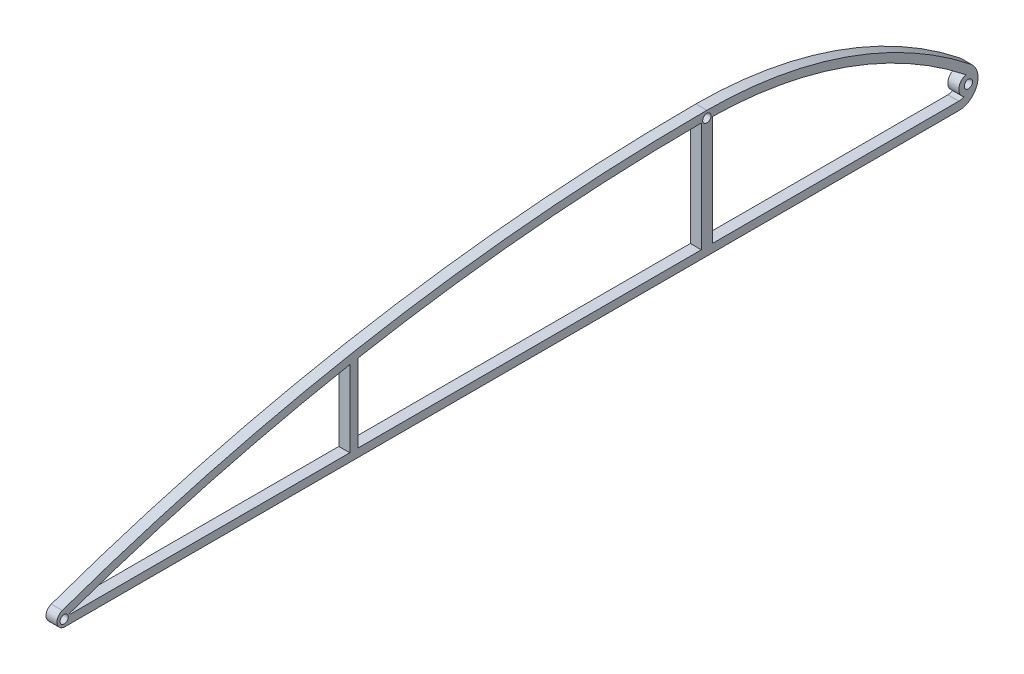
SolidWorks part; units mm, degrees
other "Marquage1"
sketch "Esquisse8" plane through (8, 0, -172.8424) normal (1, 0, 0) x (0, 0, -1)
other "Marquage2"
sketch "Esquisse10" plane through (-6, 20, -172.8424) normal (-0.8365, 0.2588, -0.483) x (-0.5, 0, 0.866)
other "Marquage3"
sketch "Esquisse11" plane through (0, 0, 0) normal (-0.0501, -0.1345, 0.9896) x (0.9942, 0.0873, 0.0622)
ref_plane "Plan de face" through (0, 0, 0) normal (0, 0, 1) x (1, 0, 0)
ref_plane "Plan de dessus" through (0, 0, 0) normal (0, 1, 0) x (1, 0, 0)
ref_plane "Plan de droite" through (0, 0, 0) normal (1, 0, 0) x (0, 0, -1)
sketch "Esquisse2" plane through (0, 0, 0) normal (1, 0, 0) x (0, 0, -1)
  line L0 (0, 0) -> (170.8732, 0)
  arc A1 (173.0499, 6.2408) -> (125, 23) centre (125, -54.2609) ccw
  arc A3 (170.8732, 0) -> (173.0499, 6.2408) centre (170.8732, 3.5) ccw
  arc A4 (125, 23) -> (0, 0) centre (125, -328.1739) ccw
  point P10 (180, 0)
  dimension "D1" = 180
  dimension "D2" = 3.5
  dimension "D3" = 23
  dimension "D4" = 55
extrude "Boss.-Extru.1" add sketch "Esquisse2" along normal blind 2
sketch "Esquisse4" plane through (2, 0, 0) normal (1, 0, 0) x (0, 0, -1)
  line L0 (125, 23) -> (125, 21.75) construction
  line L1 (0, 0) -> (8, 1.25) construction
  line L10 (174.369, 3.3283) -> (172.619, 3.3283) construction
  circle A6 centre (125, 21.75) radius 0.75
  circle A12 centre (172.619, 3.3283) radius 0.75
  arc A13 (170.8732, 0) -> (173.0499, 6.2408) centre (170.8732, 3.5) ccw construction
  circle A15 centre (8, 1.25) radius 0.75
  dimension "D1" = 1.5
  dimension "D2" = 1.5
  dimension "D7" = 1.5
  dimension "D3" = 1.25
  dimension "D4" = 8
  dimension "D5" = 1.25
  dimension "D6" = 1.75
extrude "Enlèv. mat.-Extru.2" cut sketch "Esquisse4" against normal through all
sketch "Esquisse9" plane through (0, 0, 0) normal (1, 0, 0) x (0, 0, -1)
  line L26 (126, 1.5) -> (170.8732, 1.5)
  line L35 (8.4369, 1.5) -> (170.8732, 1.5)
  line L36 (9.0712, 1.5) -> (60, 1.5)
  line L37 (124, 21.4417) -> (124, 1.5)
  line L39 (126, 21.4417) -> (126, 1.5)
  line L40 (61.5, 1.5) -> (124, 1.5)
  line L42 (60, 1.5) -> (60, 15.4055)
  line L44 (61.5, 1.5) -> (61.5, 15.6859)
  arc A12 (172.1725, 5.0204) -> (172.117, 5.0662) centre (170.8732, 3.5) ccw
  arc A18 (126, 21.4417) -> (126.022, 21.4931) centre (125, 21.9) ccw
  arc A20 (60, 15.4055) -> (9.0038, 1.6999) centre (125, -328.1739) ccw
  circle A30 centre (125, 21.9) radius 1.1
  arc A35 (170.8732, 1.5) -> (172.117, 5.0662) centre (170.8732, 3.5) ccw
  arc A39 (172.117, 5.0662) -> (125, 21.5) centre (125, -54.2609) ccw
  arc A40 (125, 21.5) -> (8.4369, 1.5) centre (125, -328.1739) ccw
  arc A41 (170.8732, 1.5) -> (171.8515, 1.7556) centre (170.8732, 3.5) ccw
  arc A42 (172.117, 5.0662) -> (126.022, 21.4931) centre (125, -54.2609) ccw
  arc A43 (123.9759, 21.4985) -> (61.5, 15.6859) centre (125, -328.1739) ccw
  arc A44 (123.9759, 21.4985) -> (124, 21.4417) centre (125, 21.9) ccw
  circle A46 centre (172.619, 3.3283) radius 1.75
  arc A49 (172.1725, 5.0204) -> (171.8515, 1.7556) centre (172.619, 3.3283) ccw
  circle A53 centre (8, 1.25) radius 1.1
  arc A54 (9.0712, 1.5) -> (9.0038, 1.6999) centre (8, 1.25) ccw
  dimension "D1" = 1.5
  dimension "D2" = 0.5
  dimension "D3" = 0.5
  dimension "D5" = 2
  dimension "D4" = 0.5
  dimension "D6" = 1.5
  dimension "D7" = 60
extrude "Enlèv. mat.-Extru.3" cut sketch "Esquisse9" along normal blind 4
fillet "Congé2" radius 1.45 1 edges at (1, 0, 0)
